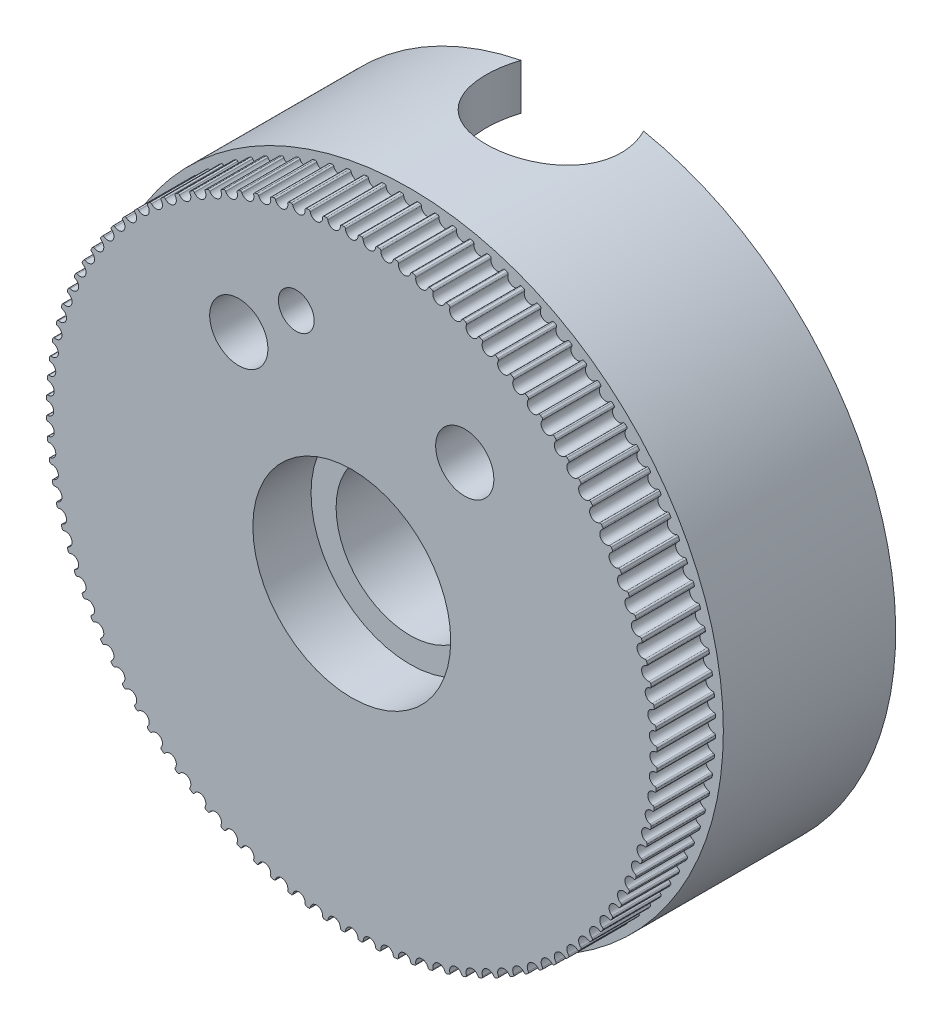
SolidWorks part; units mm, degrees
ref_plane "前视基准面" through (0, 0, 0) normal (0, 0, 1) x (1, 0, 0)
ref_plane "上视基准面" through (0, 0, 0) normal (0, 1, 0) x (1, 0, 0)
ref_plane "右视基准面" through (0, 0, 0) normal (1, 0, 0) x (0, 0, -1)
sketch "草图1" plane through (0, 0, 0) normal (0, 0, 1) x (1, 0, 0)
  circle A0 centre (0, 0) radius 35
  circle A1 centre (0, 0) radius 8.25
  dimension "D1" = 70
  dimension "D2" = 16.5
extrude "凸台-拉伸1" add sketch "草图1" along normal blind 19.25
ref_plane "基准面1" through (0, 14, 0) normal (0, 1, 0) x (1, 0, 0)
sketch "草图2" plane through (0, 14, 0) normal (0, 1, 0) x (1, 0, 0)
  line L0 (35, 0) -> (-35, 0) construction
  circle A0 centre (0, -3.2) radius 7.55
  dimension "D1" = 15.1
  dimension "D2" = 3.2
extrude "切除-拉伸1" cut sketch "草图2" along normal through all
sketch "草图3" plane through (0, 0, 0) normal (0, 0, -1) x (-1, 0, 0)
  circle A0 centre (0, 0) radius 14.5
  circle A1 centre (0, 0) radius 30
  dimension "D1" = 60
  dimension "D2" = 29
extrude "切除-拉伸2" cut sketch "草图3" against normal blind 8.75
sketch "草图4" plane through (0, 0, 19.25) normal (0, 0, 1) x (1, 0, 0)
  circle A0 centre (0, 0) radius 8.25 construction
  circle A1 centre (0, 0) radius 8.25
  arc B0 (1.1216, 34.1041) -> (0.8633, 34.1116) centre (0, 0) ccw
  arc B1 (1.2763, 33.9415) -> (1.1216, 34.1041) centre (1.1163, 33.9441) ccw
  arc B2 (0.8633, 34.1116) -> (0.6994, 33.9583) centre (0.8593, 33.9516) ccw
  arc B3 (1.2763, 33.9415) -> (2.6727, 33.8602) centre (1.9762, 33.93) ccw
  arc B4 (-0.8633, 34.1116) -> (-1.1216, 34.1041) centre (0, 0) ccw
  arc B5 (-0.6994, 33.9583) -> (-0.8633, 34.1116) centre (-0.8593, 33.9516) ccw
  arc B6 (-1.1216, 34.1041) -> (-1.2763, 33.9415) centre (-1.1163, 33.9441) ccw
  arc B7 (-0.6994, 33.9583) -> (0.6994, 33.9583) centre (0, 33.9875) ccw
  arc B8 (-2.8453, 34.0037) -> (-3.1027, 33.9812) centre (0, 0) ccw
  arc B9 (-2.6727, 33.8602) -> (-2.8453, 34.0037) centre (-2.8319, 33.8442) ccw
  arc B10 (-3.1027, 33.9812) -> (-3.2477, 33.8099) centre (-3.0881, 33.8218) ccw
  arc B11 (-2.6727, 33.8602) -> (-1.2763, 33.9415) centre (-1.9762, 33.93) ccw
  arc B12 (-4.8176, 33.7807) -> (-5.0732, 33.7433) centre (0, 0) ccw
  arc B13 (-4.637, 33.6475) -> (-4.8176, 33.7807) centre (-4.795, 33.6223) ccw
  arc B14 (-5.0732, 33.7433) -> (-5.208, 33.5638) centre (-5.0494, 33.585) ccw
  arc B15 (-4.637, 33.6475) -> (-3.2477, 33.8099) centre (-3.9457, 33.7577) ccw
  arc B16 (-6.7736, 33.4434) -> (-7.0266, 33.3912) centre (0, 0) ccw
  arc B17 (-6.5856, 33.321) -> (-6.7736, 33.4434) centre (-6.7418, 33.2866) ccw
  arc B18 (-7.0266, 33.3912) -> (-7.1508, 33.2042) centre (-6.9937, 33.2346) ccw
  arc B19 (-6.5856, 33.321) -> (-5.208, 33.5638) centre (-5.9019, 33.4712) ccw
  arc B20 (-8.7067, 32.993) -> (-8.9563, 32.9261) centre (0, 0) ccw
  arc B21 (-8.5119, 32.8817) -> (-8.7067, 32.993) centre (-8.6659, 32.8383) ccw
  arc B22 (-8.9563, 32.9261) -> (-9.0693, 32.7323) centre (-8.9143, 32.7717) ccw
  arc B23 (-8.5119, 32.8817) -> (-7.1508, 33.2042) centre (-7.8381, 33.0714) ccw
  arc B24 (-10.6103, 32.4309) -> (-10.8556, 32.3497) centre (0, 0) ccw
  arc B25 (-10.4094, 32.3311) -> (-10.6103, 32.4309) centre (-10.5606, 32.2789) ccw
  arc B26 (-10.8556, 32.3497) -> (-10.9572, 32.1496) centre (-10.8047, 32.198) ccw
  arc B27 (-10.4094, 32.3311) -> (-9.0693, 32.7323) centre (-9.7477, 32.5597) ccw
  arc B28 (-12.4781, 31.7591) -> (-12.7182, 31.6637) centre (0, 0) ccw
  arc B29 (-12.2716, 31.6712) -> (-12.4781, 31.7591) centre (-12.4196, 31.6102) ccw
  arc B30 (-12.7182, 31.6637) -> (-12.808, 31.4581) centre (-12.6586, 31.5153) ccw
  arc B31 (-12.2716, 31.6712) -> (-10.9572, 32.1496) centre (-11.6244, 31.9378) ccw
  arc B32 (-14.3036, 30.9799) -> (-14.5378, 30.8707) centre (0, 0) ccw
  arc B33 (-14.0924, 30.904) -> (-14.3036, 30.9799) centre (-14.2365, 30.8346) ccw
  arc B34 (-14.5378, 30.8707) -> (-14.6155, 30.6601) centre (-14.4696, 30.7259) ccw
  arc B35 (-14.0924, 30.904) -> (-12.808, 31.4581) centre (-13.4618, 31.2079) ccw
  arc B36 (-16.0807, 30.0958) -> (-16.3081, 29.9731) centre (0, 0) ccw
  arc B37 (-15.8655, 30.0324) -> (-16.0807, 30.0958) centre (-16.0053, 29.9547) ccw
  arc B38 (-16.3081, 29.9731) -> (-16.3735, 29.7584) centre (-16.2317, 29.8326) ccw
  arc B39 (-15.8655, 30.0324) -> (-14.6155, 30.6601) centre (-15.2536, 30.3723) ccw
  arc B40 (-17.8034, 29.1098) -> (-18.0233, 28.9742) centre (0, 0) ccw
  arc B41 (-17.5848, 29.0591) -> (-17.8034, 29.1098) centre (-17.7199, 28.9733) ccw
  arc B42 (-18.0233, 28.9742) -> (-18.0761, 28.7561) centre (-17.9388, 28.8383) ccw
  arc B43 (-17.5848, 29.0591) -> (-16.3735, 29.7584) centre (-16.9937, 29.434) ccw
  arc B44 (-19.4659, 28.0254) -> (-19.6775, 27.8772) centre (0, 0) ccw
  arc B45 (-19.2447, 27.9874) -> (-19.4659, 28.0254) centre (-19.3746, 27.894) ccw
  arc B46 (-19.6775, 27.8772) -> (-19.7175, 27.6564) centre (-19.5853, 27.7465) ccw
  arc B47 (-19.2447, 27.9874) -> (-18.0761, 28.7561) centre (-18.6764, 28.3961) ccw
  arc B48 (-21.0625, 26.8462) -> (-21.2652, 26.6859) centre (0, 0) ccw
  arc B49 (-20.8395, 26.8211) -> (-21.0625, 26.8462) centre (-20.9637, 26.7203) ccw
  arc B50 (-21.2652, 26.6859) -> (-21.2922, 26.4631) centre (-21.1655, 26.5608) ccw
  arc B51 (-20.8395, 26.8211) -> (-19.7175, 27.6564) centre (-20.2959, 27.2622) ccw
  arc B52 (-22.5878, 25.5761) -> (-22.7808, 25.4043) centre (0, 0) ccw
  arc B53 (-22.3637, 25.564) -> (-22.5878, 25.5761) centre (-22.4819, 25.4561) ccw
  arc B54 (-22.7808, 25.4043) -> (-22.7949, 25.1803) centre (-22.674, 25.2852) ccw
  arc B55 (-22.3637, 25.564) -> (-21.2922, 26.4631) centre (-21.8467, 26.0359) ccw
  arc B56 (-24.0367, 24.2194) -> (-24.2194, 24.0367) centre (0, 0) ccw
  arc B57 (-23.8123, 24.2204) -> (-24.0367, 24.2194) centre (-23.924, 24.1059) ccw
  arc B58 (-24.2194, 24.0367) -> (-24.2204, 23.8123) centre (-24.1059, 23.924) ccw
  arc B59 (-23.8123, 24.2204) -> (-22.7949, 25.1803) centre (-23.3236, 24.7216) ccw
  arc B60 (-25.4043, 22.7808) -> (-25.5761, 22.5878) centre (0, 0) ccw
  arc B61 (-25.1803, 22.7949) -> (-25.4043, 22.7808) centre (-25.2852, 22.674) ccw
  arc B62 (-25.5761, 22.5878) -> (-25.564, 22.3637) centre (-25.4561, 22.4819) ccw
  arc B63 (-25.1803, 22.7949) -> (-24.2204, 23.8123) centre (-24.7216, 23.3236) ccw
  arc B64 (-26.6859, 21.2652) -> (-26.8462, 21.0625) centre (0, 0) ccw
  arc B65 (-26.4631, 21.2922) -> (-26.6859, 21.2652) centre (-26.5608, 21.1655) ccw
  arc B66 (-26.8462, 21.0625) -> (-26.8211, 20.8395) centre (-26.7203, 20.9637) ccw
  arc B67 (-26.4631, 21.2922) -> (-25.564, 22.3637) centre (-26.0359, 21.8467) ccw
  arc B68 (-27.8772, 19.6775) -> (-28.0254, 19.4659) centre (0, 0) ccw
  arc B69 (-27.6564, 19.7175) -> (-27.8772, 19.6775) centre (-27.7465, 19.5853) ccw
  arc B70 (-28.0254, 19.4659) -> (-27.9874, 19.2447) centre (-27.894, 19.3746) ccw
  arc B71 (-27.6564, 19.7175) -> (-26.8211, 20.8395) centre (-27.2622, 20.2959) ccw
  arc B72 (-28.9742, 18.0233) -> (-29.1098, 17.8034) centre (0, 0) ccw
  arc B73 (-28.7561, 18.0761) -> (-28.9742, 18.0233) centre (-28.8383, 17.9388) ccw
  arc B74 (-29.1098, 17.8034) -> (-29.0591, 17.5848) centre (-28.9733, 17.7199) ccw
  arc B75 (-28.7561, 18.0761) -> (-27.9874, 19.2447) centre (-28.3961, 18.6764) ccw
  arc B76 (-29.9731, 16.3081) -> (-30.0958, 16.0807) centre (0, 0) ccw
  arc B77 (-29.7584, 16.3735) -> (-29.9731, 16.3081) centre (-29.8326, 16.2317) ccw
  arc B78 (-30.0958, 16.0807) -> (-30.0324, 15.8655) centre (-29.9547, 16.0053) ccw
  arc B79 (-29.7584, 16.3735) -> (-29.0591, 17.5848) centre (-29.434, 16.9937) ccw
  arc B80 (-30.8707, 14.5378) -> (-30.9799, 14.3036) centre (0, 0) ccw
  arc B81 (-30.6601, 14.6155) -> (-30.8707, 14.5378) centre (-30.7259, 14.4696) ccw
  arc B82 (-30.9799, 14.3036) -> (-30.904, 14.0924) centre (-30.8346, 14.2365) ccw
  arc B83 (-30.6601, 14.6155) -> (-30.0324, 15.8655) centre (-30.3723, 15.2536) ccw
  arc B84 (-31.6637, 12.7182) -> (-31.7591, 12.4781) centre (0, 0) ccw
  arc B85 (-31.4581, 12.808) -> (-31.6637, 12.7182) centre (-31.5153, 12.6586) ccw
  arc B86 (-31.7591, 12.4781) -> (-31.6712, 12.2716) centre (-31.6102, 12.4196) ccw
  arc B87 (-31.4581, 12.808) -> (-30.904, 14.0924) centre (-31.2079, 13.4618) ccw
  arc B88 (-32.3497, 10.8556) -> (-32.4309, 10.6103) centre (0, 0) ccw
  arc B89 (-32.1496, 10.9572) -> (-32.3497, 10.8556) centre (-32.198, 10.8047) ccw
  arc B90 (-32.4309, 10.6103) -> (-32.3311, 10.4094) centre (-32.2789, 10.5606) ccw
  arc B91 (-32.1496, 10.9572) -> (-31.6712, 12.2716) centre (-31.9378, 11.6244) ccw
  arc B92 (-32.9261, 8.9563) -> (-32.993, 8.7067) centre (0, 0) ccw
  arc B93 (-32.7323, 9.0693) -> (-32.9261, 8.9563) centre (-32.7717, 8.9143) ccw
  arc B94 (-32.993, 8.7067) -> (-32.8817, 8.5119) centre (-32.8383, 8.6659) ccw
  arc B95 (-32.7323, 9.0693) -> (-32.3311, 10.4094) centre (-32.5597, 9.7477) ccw
  arc B96 (-33.3912, 7.0266) -> (-33.4434, 6.7736) centre (0, 0) ccw
  arc B97 (-33.2042, 7.1508) -> (-33.3912, 7.0266) centre (-33.2346, 6.9937) ccw
  arc B98 (-33.4434, 6.7736) -> (-33.321, 6.5856) centre (-33.2866, 6.7418) ccw
  arc B99 (-33.2042, 7.1508) -> (-32.8817, 8.5119) centre (-33.0714, 7.8381) ccw
  arc B100 (-33.7433, 5.0732) -> (-33.7807, 4.8176) centre (0, 0) ccw
  arc B101 (-33.5638, 5.208) -> (-33.7433, 5.0732) centre (-33.585, 5.0494) ccw
  arc B102 (-33.7807, 4.8176) -> (-33.6475, 4.637) centre (-33.6223, 4.795) ccw
  arc B103 (-33.5638, 5.208) -> (-33.321, 6.5856) centre (-33.4712, 5.9019) ccw
  arc B104 (-33.9812, 3.1027) -> (-34.0037, 2.8453) centre (0, 0) ccw
  arc B105 (-33.8099, 3.2477) -> (-33.9812, 3.1027) centre (-33.8218, 3.0881) ccw
  arc B106 (-34.0037, 2.8453) -> (-33.8602, 2.6727) centre (-33.8442, 2.8319) ccw
  arc B107 (-33.8099, 3.2477) -> (-33.6475, 4.637) centre (-33.7577, 3.9457) ccw
  arc B108 (-34.1041, 1.1216) -> (-34.1116, 0.8633) centre (0, 0) ccw
  arc B109 (-33.9415, 1.2763) -> (-34.1041, 1.1216) centre (-33.9441, 1.1163) ccw
  arc B110 (-34.1116, 0.8633) -> (-33.9583, 0.6994) centre (-33.9516, 0.8593) ccw
  arc B111 (-33.9415, 1.2763) -> (-33.8602, 2.6727) centre (-33.93, 1.9762) ccw
  arc B112 (-34.1116, -0.8633) -> (-34.1041, -1.1216) centre (0, 0) ccw
  arc B113 (-33.9583, -0.6994) -> (-34.1116, -0.8633) centre (-33.9516, -0.8593) ccw
  arc B114 (-34.1041, -1.1216) -> (-33.9415, -1.2763) centre (-33.9441, -1.1163) ccw
  arc B115 (-33.9583, -0.6994) -> (-33.9583, 0.6994) centre (-33.9875, 0) ccw
  arc B116 (-34.0037, -2.8453) -> (-33.9812, -3.1027) centre (0, 0) ccw
  arc B117 (-33.8602, -2.6727) -> (-34.0037, -2.8453) centre (-33.8442, -2.8319) ccw
  arc B118 (-33.9812, -3.1027) -> (-33.8099, -3.2477) centre (-33.8218, -3.0881) ccw
  arc B119 (-33.8602, -2.6727) -> (-33.9415, -1.2763) centre (-33.93, -1.9762) ccw
  arc B120 (-33.7807, -4.8176) -> (-33.7433, -5.0732) centre (0, 0) ccw
  arc B121 (-33.6475, -4.637) -> (-33.7807, -4.8176) centre (-33.6223, -4.795) ccw
  arc B122 (-33.7433, -5.0732) -> (-33.5638, -5.208) centre (-33.585, -5.0494) ccw
  arc B123 (-33.6475, -4.637) -> (-33.8099, -3.2477) centre (-33.7577, -3.9457) ccw
  arc B124 (-33.4434, -6.7736) -> (-33.3912, -7.0266) centre (0, 0) ccw
  arc B125 (-33.321, -6.5856) -> (-33.4434, -6.7736) centre (-33.2866, -6.7418) ccw
  arc B126 (-33.3912, -7.0266) -> (-33.2042, -7.1508) centre (-33.2346, -6.9937) ccw
  arc B127 (-33.321, -6.5856) -> (-33.5638, -5.208) centre (-33.4712, -5.9019) ccw
  arc B128 (-32.993, -8.7067) -> (-32.9261, -8.9563) centre (0, 0) ccw
  arc B129 (-32.8817, -8.5119) -> (-32.993, -8.7067) centre (-32.8383, -8.6659) ccw
  arc B130 (-32.9261, -8.9563) -> (-32.7323, -9.0693) centre (-32.7717, -8.9143) ccw
  arc B131 (-32.8817, -8.5119) -> (-33.2042, -7.1508) centre (-33.0714, -7.8381) ccw
  arc B132 (-32.4309, -10.6103) -> (-32.3497, -10.8556) centre (0, 0) ccw
  arc B133 (-32.3311, -10.4094) -> (-32.4309, -10.6103) centre (-32.2789, -10.5606) ccw
  arc B134 (-32.3497, -10.8556) -> (-32.1496, -10.9572) centre (-32.198, -10.8047) ccw
  arc B135 (-32.3311, -10.4094) -> (-32.7323, -9.0693) centre (-32.5597, -9.7477) ccw
  arc B136 (-31.7591, -12.4781) -> (-31.6637, -12.7182) centre (0, 0) ccw
  arc B137 (-31.6712, -12.2716) -> (-31.7591, -12.4781) centre (-31.6102, -12.4196) ccw
  arc B138 (-31.6637, -12.7182) -> (-31.4581, -12.808) centre (-31.5153, -12.6586) ccw
  arc B139 (-31.6712, -12.2716) -> (-32.1496, -10.9572) centre (-31.9378, -11.6244) ccw
  arc B140 (-30.9799, -14.3036) -> (-30.8707, -14.5378) centre (0, 0) ccw
  arc B141 (-30.904, -14.0924) -> (-30.9799, -14.3036) centre (-30.8346, -14.2365) ccw
  arc B142 (-30.8707, -14.5378) -> (-30.6601, -14.6155) centre (-30.7259, -14.4696) ccw
  arc B143 (-30.904, -14.0924) -> (-31.4581, -12.808) centre (-31.2079, -13.4618) ccw
  arc B144 (-30.0958, -16.0807) -> (-29.9731, -16.3081) centre (0, 0) ccw
  arc B145 (-30.0324, -15.8655) -> (-30.0958, -16.0807) centre (-29.9547, -16.0053) ccw
  arc B146 (-29.9731, -16.3081) -> (-29.7584, -16.3735) centre (-29.8326, -16.2317) ccw
  arc B147 (-30.0324, -15.8655) -> (-30.6601, -14.6155) centre (-30.3723, -15.2536) ccw
  arc B148 (-29.1098, -17.8034) -> (-28.9742, -18.0233) centre (0, 0) ccw
  arc B149 (-29.0591, -17.5848) -> (-29.1098, -17.8034) centre (-28.9733, -17.7199) ccw
  arc B150 (-28.9742, -18.0233) -> (-28.7561, -18.0761) centre (-28.8383, -17.9388) ccw
  arc B151 (-29.0591, -17.5848) -> (-29.7584, -16.3735) centre (-29.434, -16.9938) ccw
  arc B152 (-28.0254, -19.4659) -> (-27.8772, -19.6775) centre (0, 0) ccw
  arc B153 (-27.9874, -19.2447) -> (-28.0254, -19.4659) centre (-27.894, -19.3746) ccw
  arc B154 (-27.8772, -19.6775) -> (-27.6564, -19.7175) centre (-27.7465, -19.5853) ccw
  arc B155 (-27.9874, -19.2447) -> (-28.7561, -18.0761) centre (-28.3961, -18.6764) ccw
  arc B156 (-26.8462, -21.0625) -> (-26.6859, -21.2652) centre (0, 0) ccw
  arc B157 (-26.8211, -20.8395) -> (-26.8462, -21.0625) centre (-26.7203, -20.9637) ccw
  arc B158 (-26.6859, -21.2652) -> (-26.4631, -21.2922) centre (-26.5608, -21.1655) ccw
  arc B159 (-26.8211, -20.8395) -> (-27.6564, -19.7175) centre (-27.2622, -20.2959) ccw
  arc B160 (-25.5761, -22.5878) -> (-25.4043, -22.7808) centre (0, 0) ccw
  arc B161 (-25.564, -22.3637) -> (-25.5761, -22.5878) centre (-25.4561, -22.4819) ccw
  arc B162 (-25.4043, -22.7808) -> (-25.1803, -22.7949) centre (-25.2852, -22.674) ccw
  arc B163 (-25.564, -22.3637) -> (-26.4631, -21.2922) centre (-26.0359, -21.8467) ccw
  arc B164 (-24.2194, -24.0367) -> (-24.0367, -24.2194) centre (0, 0) ccw
  arc B165 (-24.2204, -23.8123) -> (-24.2194, -24.0367) centre (-24.1059, -23.924) ccw
  arc B166 (-24.0367, -24.2194) -> (-23.8123, -24.2204) centre (-23.924, -24.1059) ccw
  arc B167 (-24.2204, -23.8123) -> (-25.1803, -22.7949) centre (-24.7216, -23.3236) ccw
  arc B168 (-22.7808, -25.4043) -> (-22.5878, -25.5761) centre (0, 0) ccw
  arc B169 (-22.7949, -25.1803) -> (-22.7808, -25.4043) centre (-22.674, -25.2852) ccw
  arc B170 (-22.5878, -25.5761) -> (-22.3637, -25.564) centre (-22.4819, -25.4561) ccw
  arc B171 (-22.7949, -25.1803) -> (-23.8123, -24.2204) centre (-23.3236, -24.7216) ccw
  arc B172 (-21.2652, -26.6859) -> (-21.0625, -26.8462) centre (0, 0) ccw
  arc B173 (-21.2922, -26.4631) -> (-21.2652, -26.6859) centre (-21.1655, -26.5608) ccw
  arc B174 (-21.0625, -26.8462) -> (-20.8395, -26.8211) centre (-20.9637, -26.7203) ccw
  arc B175 (-21.2922, -26.4631) -> (-22.3637, -25.564) centre (-21.8467, -26.0359) ccw
  arc B176 (-19.6775, -27.8772) -> (-19.4659, -28.0254) centre (0, 0) ccw
  arc B177 (-19.7175, -27.6564) -> (-19.6775, -27.8772) centre (-19.5853, -27.7465) ccw
  arc B178 (-19.4659, -28.0254) -> (-19.2447, -27.9874) centre (-19.3746, -27.894) ccw
  arc B179 (-19.7175, -27.6564) -> (-20.8395, -26.8211) centre (-20.2959, -27.2622) ccw
  arc B180 (-18.0233, -28.9742) -> (-17.8034, -29.1098) centre (0, 0) ccw
  arc B181 (-18.0761, -28.7561) -> (-18.0233, -28.9742) centre (-17.9388, -28.8383) ccw
  arc B182 (-17.8034, -29.1098) -> (-17.5848, -29.0591) centre (-17.7199, -28.9733) ccw
  arc B183 (-18.0761, -28.7561) -> (-19.2447, -27.9874) centre (-18.6764, -28.3961) ccw
  arc B184 (-16.3081, -29.9731) -> (-16.0807, -30.0958) centre (0, 0) ccw
  arc B185 (-16.3735, -29.7584) -> (-16.3081, -29.9731) centre (-16.2317, -29.8326) ccw
  arc B186 (-16.0807, -30.0958) -> (-15.8655, -30.0324) centre (-16.0053, -29.9547) ccw
  arc B187 (-16.3735, -29.7584) -> (-17.5848, -29.0591) centre (-16.9937, -29.434) ccw
  arc B188 (-14.5378, -30.8707) -> (-14.3036, -30.9799) centre (0, 0) ccw
  arc B189 (-14.6155, -30.6601) -> (-14.5378, -30.8707) centre (-14.4696, -30.7259) ccw
  arc B190 (-14.3036, -30.9799) -> (-14.0924, -30.904) centre (-14.2365, -30.8346) ccw
  arc B191 (-14.6155, -30.6601) -> (-15.8655, -30.0324) centre (-15.2536, -30.3723) ccw
  arc B192 (-12.7182, -31.6637) -> (-12.4781, -31.7591) centre (0, 0) ccw
  arc B193 (-12.808, -31.4581) -> (-12.7182, -31.6637) centre (-12.6586, -31.5153) ccw
  arc B194 (-12.4781, -31.7591) -> (-12.2716, -31.6712) centre (-12.4196, -31.6102) ccw
  arc B195 (-12.808, -31.4581) -> (-14.0924, -30.904) centre (-13.4618, -31.2079) ccw
  arc B196 (-10.8556, -32.3497) -> (-10.6103, -32.4309) centre (0, 0) ccw
  arc B197 (-10.9572, -32.1496) -> (-10.8556, -32.3497) centre (-10.8047, -32.198) ccw
  arc B198 (-10.6103, -32.4309) -> (-10.4094, -32.3311) centre (-10.5606, -32.2789) ccw
  arc B199 (-10.9572, -32.1496) -> (-12.2716, -31.6712) centre (-11.6244, -31.9378) ccw
  arc B200 (-8.9563, -32.9261) -> (-8.7067, -32.993) centre (0, 0) ccw
  arc B201 (-9.0693, -32.7323) -> (-8.9563, -32.9261) centre (-8.9143, -32.7717) ccw
  arc B202 (-8.7067, -32.993) -> (-8.5119, -32.8817) centre (-8.6659, -32.8383) ccw
  arc B203 (-9.0693, -32.7323) -> (-10.4094, -32.3311) centre (-9.7477, -32.5597) ccw
  arc B204 (-7.0266, -33.3912) -> (-6.7736, -33.4434) centre (0, 0) ccw
  arc B205 (-7.1508, -33.2042) -> (-7.0266, -33.3912) centre (-6.9937, -33.2346) ccw
  arc B206 (-6.7736, -33.4434) -> (-6.5856, -33.321) centre (-6.7418, -33.2866) ccw
  arc B207 (-7.1508, -33.2042) -> (-8.5119, -32.8817) centre (-7.8381, -33.0714) ccw
  arc B208 (-5.0732, -33.7433) -> (-4.8176, -33.7807) centre (0, 0) ccw
  arc B209 (-5.208, -33.5638) -> (-5.0732, -33.7433) centre (-5.0494, -33.585) ccw
  arc B210 (-4.8176, -33.7807) -> (-4.637, -33.6475) centre (-4.795, -33.6223) ccw
  arc B211 (-5.208, -33.5638) -> (-6.5856, -33.321) centre (-5.9019, -33.4712) ccw
  arc B212 (-3.1027, -33.9812) -> (-2.8453, -34.0037) centre (0, 0) ccw
  arc B213 (-3.2477, -33.8099) -> (-3.1027, -33.9812) centre (-3.0881, -33.8218) ccw
  arc B214 (-2.8453, -34.0037) -> (-2.6727, -33.8602) centre (-2.8319, -33.8442) ccw
  arc B215 (-3.2477, -33.8099) -> (-4.637, -33.6475) centre (-3.9457, -33.7577) ccw
  arc B216 (-1.1216, -34.1041) -> (-0.8633, -34.1116) centre (0, 0) ccw
  arc B217 (-1.2763, -33.9415) -> (-1.1216, -34.1041) centre (-1.1163, -33.9441) ccw
  arc B218 (-0.8633, -34.1116) -> (-0.6994, -33.9583) centre (-0.8593, -33.9516) ccw
  arc B219 (-1.2763, -33.9415) -> (-2.6727, -33.8602) centre (-1.9762, -33.93) ccw
  arc B220 (0.8633, -34.1116) -> (1.1216, -34.1041) centre (0, 0) ccw
  arc B221 (0.6994, -33.9583) -> (0.8633, -34.1116) centre (0.8593, -33.9516) ccw
  arc B222 (1.1216, -34.1041) -> (1.2763, -33.9415) centre (1.1163, -33.9441) ccw
  arc B223 (0.6994, -33.9583) -> (-0.6994, -33.9583) centre (0, -33.9875) ccw
  arc B224 (2.8453, -34.0037) -> (3.1027, -33.9812) centre (0, 0) ccw
  arc B225 (2.6727, -33.8602) -> (2.8453, -34.0037) centre (2.8319, -33.8442) ccw
  arc B226 (3.1027, -33.9812) -> (3.2477, -33.8099) centre (3.0881, -33.8218) ccw
  arc B227 (2.6727, -33.8602) -> (1.2763, -33.9415) centre (1.9762, -33.93) ccw
  arc B228 (4.8176, -33.7807) -> (5.0732, -33.7433) centre (0, 0) ccw
  arc B229 (4.637, -33.6475) -> (4.8176, -33.7807) centre (4.795, -33.6223) ccw
  arc B230 (5.0732, -33.7433) -> (5.208, -33.5638) centre (5.0494, -33.585) ccw
  arc B231 (4.637, -33.6475) -> (3.2477, -33.8099) centre (3.9457, -33.7577) ccw
  arc B232 (6.7736, -33.4434) -> (7.0266, -33.3912) centre (0, 0) ccw
  arc B233 (6.5856, -33.321) -> (6.7736, -33.4434) centre (6.7418, -33.2866) ccw
  arc B234 (7.0266, -33.3912) -> (7.1508, -33.2042) centre (6.9937, -33.2346) ccw
  arc B235 (6.5856, -33.321) -> (5.208, -33.5638) centre (5.9019, -33.4712) ccw
  arc B236 (8.7067, -32.993) -> (8.9563, -32.9261) centre (0, 0) ccw
  arc B237 (8.5119, -32.8817) -> (8.7067, -32.993) centre (8.6659, -32.8383) ccw
  arc B238 (8.9563, -32.9261) -> (9.0693, -32.7323) centre (8.9143, -32.7717) ccw
  arc B239 (8.5119, -32.8817) -> (7.1508, -33.2042) centre (7.8381, -33.0714) ccw
  arc B240 (10.6103, -32.4309) -> (10.8556, -32.3497) centre (0, 0) ccw
  arc B241 (10.4094, -32.3311) -> (10.6103, -32.4309) centre (10.5606, -32.2789) ccw
  arc B242 (10.8556, -32.3497) -> (10.9572, -32.1496) centre (10.8047, -32.198) ccw
  arc B243 (10.4094, -32.3311) -> (9.0693, -32.7323) centre (9.7477, -32.5597) ccw
  arc B244 (12.4781, -31.7591) -> (12.7182, -31.6637) centre (0, 0) ccw
  arc B245 (12.2716, -31.6712) -> (12.4781, -31.7591) centre (12.4196, -31.6102) ccw
  arc B246 (12.7182, -31.6637) -> (12.808, -31.4581) centre (12.6586, -31.5153) ccw
  arc B247 (12.2716, -31.6712) -> (10.9572, -32.1496) centre (11.6244, -31.9378) ccw
  arc B248 (14.3036, -30.9799) -> (14.5378, -30.8707) centre (0, 0) ccw
  arc B249 (14.0924, -30.904) -> (14.3036, -30.9799) centre (14.2365, -30.8346) ccw
  arc B250 (14.5378, -30.8707) -> (14.6155, -30.6601) centre (14.4696, -30.7259) ccw
  arc B251 (14.0924, -30.904) -> (12.808, -31.4581) centre (13.4618, -31.2079) ccw
  arc B252 (16.0807, -30.0958) -> (16.3081, -29.9731) centre (0, 0) ccw
  arc B253 (15.8655, -30.0324) -> (16.0807, -30.0958) centre (16.0053, -29.9547) ccw
  arc B254 (16.3081, -29.9731) -> (16.3735, -29.7584) centre (16.2317, -29.8326) ccw
  arc B255 (15.8655, -30.0324) -> (14.6155, -30.6601) centre (15.2536, -30.3723) ccw
  arc B256 (17.8034, -29.1098) -> (18.0233, -28.9742) centre (0, 0) ccw
  arc B257 (17.5848, -29.0591) -> (17.8034, -29.1098) centre (17.7199, -28.9733) ccw
  arc B258 (18.0233, -28.9742) -> (18.0761, -28.7561) centre (17.9388, -28.8383) ccw
  arc B259 (17.5848, -29.0591) -> (16.3735, -29.7584) centre (16.9938, -29.434) ccw
  arc B260 (19.4659, -28.0254) -> (19.6775, -27.8772) centre (0, 0) ccw
  arc B261 (19.2447, -27.9874) -> (19.4659, -28.0254) centre (19.3746, -27.894) ccw
  arc B262 (19.6775, -27.8772) -> (19.7175, -27.6564) centre (19.5853, -27.7465) ccw
  arc B263 (19.2447, -27.9874) -> (18.0761, -28.7561) centre (18.6764, -28.3961) ccw
  arc B264 (21.0625, -26.8462) -> (21.2652, -26.6859) centre (0, 0) ccw
  arc B265 (20.8395, -26.8211) -> (21.0625, -26.8462) centre (20.9637, -26.7203) ccw
  arc B266 (21.2652, -26.6859) -> (21.2922, -26.4631) centre (21.1655, -26.5608) ccw
  arc B267 (20.8395, -26.8211) -> (19.7175, -27.6564) centre (20.2959, -27.2622) ccw
  arc B268 (22.5878, -25.5761) -> (22.7808, -25.4043) centre (0, 0) ccw
  arc B269 (22.3637, -25.564) -> (22.5878, -25.5761) centre (22.4819, -25.4561) ccw
  arc B270 (22.7808, -25.4043) -> (22.7949, -25.1803) centre (22.674, -25.2852) ccw
  arc B271 (22.3637, -25.564) -> (21.2922, -26.4631) centre (21.8467, -26.0359) ccw
  arc B272 (24.0367, -24.2194) -> (24.2194, -24.0367) centre (0, 0) ccw
  arc B273 (23.8123, -24.2204) -> (24.0367, -24.2194) centre (23.924, -24.1059) ccw
  arc B274 (24.2194, -24.0367) -> (24.2204, -23.8123) centre (24.1059, -23.924) ccw
  arc B275 (23.8123, -24.2204) -> (22.7949, -25.1803) centre (23.3236, -24.7216) ccw
  arc B276 (25.4043, -22.7808) -> (25.5761, -22.5878) centre (0, 0) ccw
  arc B277 (25.1803, -22.7949) -> (25.4043, -22.7808) centre (25.2852, -22.674) ccw
  arc B278 (25.5761, -22.5878) -> (25.564, -22.3637) centre (25.4561, -22.4819) ccw
  arc B279 (25.1803, -22.7949) -> (24.2204, -23.8123) centre (24.7216, -23.3236) ccw
  arc B280 (26.6859, -21.2652) -> (26.8462, -21.0625) centre (0, 0) ccw
  arc B281 (26.4631, -21.2922) -> (26.6859, -21.2652) centre (26.5608, -21.1655) ccw
  arc B282 (26.8462, -21.0625) -> (26.8211, -20.8395) centre (26.7203, -20.9637) ccw
  arc B283 (26.4631, -21.2922) -> (25.564, -22.3637) centre (26.0359, -21.8467) ccw
  arc B284 (27.8772, -19.6775) -> (28.0254, -19.4659) centre (0, 0) ccw
  arc B285 (27.6564, -19.7175) -> (27.8772, -19.6775) centre (27.7465, -19.5853) ccw
  arc B286 (28.0254, -19.4659) -> (27.9874, -19.2447) centre (27.894, -19.3746) ccw
  arc B287 (27.6564, -19.7175) -> (26.8211, -20.8395) centre (27.2622, -20.2959) ccw
  arc B288 (28.9742, -18.0233) -> (29.1098, -17.8034) centre (0, 0) ccw
  arc B289 (28.7561, -18.0761) -> (28.9742, -18.0233) centre (28.8383, -17.9388) ccw
  arc B290 (29.1098, -17.8034) -> (29.0591, -17.5848) centre (28.9733, -17.7199) ccw
  arc B291 (28.7561, -18.0761) -> (27.9874, -19.2447) centre (28.3961, -18.6764) ccw
  arc B292 (29.9731, -16.3081) -> (30.0958, -16.0807) centre (0, 0) ccw
  arc B293 (29.7584, -16.3735) -> (29.9731, -16.3081) centre (29.8326, -16.2317) ccw
  arc B294 (30.0958, -16.0807) -> (30.0324, -15.8655) centre (29.9547, -16.0053) ccw
  arc B295 (29.7584, -16.3735) -> (29.0591, -17.5848) centre (29.434, -16.9938) ccw
  arc B296 (30.8707, -14.5378) -> (30.9799, -14.3036) centre (0, 0) ccw
  arc B297 (30.6601, -14.6155) -> (30.8707, -14.5378) centre (30.7259, -14.4696) ccw
  arc B298 (30.9799, -14.3036) -> (30.904, -14.0924) centre (30.8346, -14.2365) ccw
  arc B299 (30.6601, -14.6155) -> (30.0324, -15.8655) centre (30.3723, -15.2536) ccw
  arc B300 (31.6637, -12.7182) -> (31.7591, -12.4781) centre (0, 0) ccw
  arc B301 (31.4581, -12.808) -> (31.6637, -12.7182) centre (31.5153, -12.6586) ccw
  arc B302 (31.7591, -12.4781) -> (31.6712, -12.2716) centre (31.6102, -12.4196) ccw
  arc B303 (31.4581, -12.808) -> (30.904, -14.0924) centre (31.2079, -13.4618) ccw
  arc B304 (32.3497, -10.8556) -> (32.4309, -10.6103) centre (0, 0) ccw
  arc B305 (32.1496, -10.9572) -> (32.3497, -10.8556) centre (32.198, -10.8047) ccw
  arc B306 (32.4309, -10.6103) -> (32.3311, -10.4094) centre (32.2789, -10.5606) ccw
  arc B307 (32.1496, -10.9572) -> (31.6712, -12.2716) centre (31.9378, -11.6244) ccw
  arc B308 (32.9261, -8.9563) -> (32.993, -8.7067) centre (0, 0) ccw
  arc B309 (32.7323, -9.0693) -> (32.9261, -8.9563) centre (32.7717, -8.9143) ccw
  arc B310 (32.993, -8.7067) -> (32.8817, -8.5119) centre (32.8383, -8.6659) ccw
  arc B311 (32.7323, -9.0693) -> (32.3311, -10.4094) centre (32.5597, -9.7477) ccw
  arc B312 (33.3912, -7.0266) -> (33.4434, -6.7736) centre (0, 0) ccw
  arc B313 (33.2042, -7.1508) -> (33.3912, -7.0266) centre (33.2346, -6.9937) ccw
  arc B314 (33.4434, -6.7736) -> (33.321, -6.5856) centre (33.2866, -6.7418) ccw
  arc B315 (33.2042, -7.1508) -> (32.8817, -8.5119) centre (33.0714, -7.8381) ccw
  arc B316 (33.7433, -5.0732) -> (33.7807, -4.8176) centre (0, 0) ccw
  arc B317 (33.5638, -5.208) -> (33.7433, -5.0732) centre (33.585, -5.0494) ccw
  arc B318 (33.7807, -4.8176) -> (33.6475, -4.637) centre (33.6223, -4.795) ccw
  arc B319 (33.5638, -5.208) -> (33.321, -6.5856) centre (33.4712, -5.9019) ccw
  arc B320 (33.9812, -3.1027) -> (34.0037, -2.8453) centre (0, 0) ccw
  arc B321 (33.8099, -3.2477) -> (33.9812, -3.1027) centre (33.8218, -3.0881) ccw
  arc B322 (34.0037, -2.8453) -> (33.8602, -2.6727) centre (33.8442, -2.8319) ccw
  arc B323 (33.8099, -3.2477) -> (33.6475, -4.637) centre (33.7577, -3.9457) ccw
  arc B324 (34.1041, -1.1216) -> (34.1116, -0.8633) centre (0, 0) ccw
  arc B325 (33.9415, -1.2763) -> (34.1041, -1.1216) centre (33.9441, -1.1163) ccw
  arc B326 (34.1116, -0.8633) -> (33.9583, -0.6994) centre (33.9516, -0.8593) ccw
  arc B327 (33.9415, -1.2763) -> (33.8602, -2.6727) centre (33.93, -1.9762) ccw
  arc B328 (34.1116, 0.8633) -> (34.1041, 1.1216) centre (0, 0) ccw
  arc B329 (33.9583, 0.6994) -> (34.1116, 0.8633) centre (33.9516, 0.8593) ccw
  arc B330 (34.1041, 1.1216) -> (33.9415, 1.2763) centre (33.9441, 1.1163) ccw
  arc B331 (33.9583, 0.6994) -> (33.9583, -0.6994) centre (33.9875, 0) ccw
  arc B332 (34.0037, 2.8453) -> (33.9812, 3.1027) centre (0, 0) ccw
  arc B333 (33.8602, 2.6727) -> (34.0037, 2.8453) centre (33.8442, 2.8319) ccw
  arc B334 (33.9812, 3.1027) -> (33.8099, 3.2477) centre (33.8218, 3.0881) ccw
  arc B335 (33.8602, 2.6727) -> (33.9415, 1.2763) centre (33.93, 1.9762) ccw
  arc B336 (33.7807, 4.8176) -> (33.7433, 5.0732) centre (0, 0) ccw
  arc B337 (33.6475, 4.637) -> (33.7807, 4.8176) centre (33.6223, 4.795) ccw
  arc B338 (33.7433, 5.0732) -> (33.5638, 5.208) centre (33.585, 5.0494) ccw
  arc B339 (33.6475, 4.637) -> (33.8099, 3.2477) centre (33.7577, 3.9457) ccw
  arc B340 (33.4434, 6.7736) -> (33.3912, 7.0266) centre (0, 0) ccw
  arc B341 (33.321, 6.5856) -> (33.4434, 6.7736) centre (33.2866, 6.7418) ccw
  arc B342 (33.3912, 7.0266) -> (33.2042, 7.1508) centre (33.2346, 6.9937) ccw
  arc B343 (33.321, 6.5856) -> (33.5638, 5.208) centre (33.4712, 5.9019) ccw
  arc B344 (32.993, 8.7067) -> (32.9261, 8.9563) centre (0, 0) ccw
  arc B345 (32.8817, 8.5119) -> (32.993, 8.7067) centre (32.8383, 8.6659) ccw
  arc B346 (32.9261, 8.9563) -> (32.7323, 9.0693) centre (32.7717, 8.9143) ccw
  arc B347 (32.8817, 8.5119) -> (33.2042, 7.1508) centre (33.0714, 7.8381) ccw
  arc B348 (32.4309, 10.6103) -> (32.3497, 10.8556) centre (0, 0) ccw
  arc B349 (32.3311, 10.4094) -> (32.4309, 10.6103) centre (32.2789, 10.5606) ccw
  arc B350 (32.3497, 10.8556) -> (32.1496, 10.9572) centre (32.198, 10.8047) ccw
  arc B351 (32.3311, 10.4094) -> (32.7323, 9.0693) centre (32.5597, 9.7477) ccw
  arc B352 (31.7591, 12.4781) -> (31.6637, 12.7182) centre (0, 0) ccw
  arc B353 (31.6712, 12.2716) -> (31.7591, 12.4781) centre (31.6102, 12.4196) ccw
  arc B354 (31.6637, 12.7182) -> (31.4581, 12.808) centre (31.5153, 12.6586) ccw
  arc B355 (31.6712, 12.2716) -> (32.1496, 10.9572) centre (31.9378, 11.6244) ccw
  arc B356 (30.9799, 14.3036) -> (30.8707, 14.5378) centre (0, 0) ccw
  arc B357 (30.904, 14.0924) -> (30.9799, 14.3036) centre (30.8346, 14.2365) ccw
  arc B358 (30.8707, 14.5378) -> (30.6601, 14.6155) centre (30.7259, 14.4696) ccw
  arc B359 (30.904, 14.0924) -> (31.4581, 12.808) centre (31.2079, 13.4618) ccw
  arc B360 (30.0958, 16.0807) -> (29.9731, 16.3081) centre (0, 0) ccw
  arc B361 (30.0324, 15.8655) -> (30.0958, 16.0807) centre (29.9547, 16.0053) ccw
  arc B362 (29.9731, 16.3081) -> (29.7584, 16.3735) centre (29.8326, 16.2317) ccw
  arc B363 (30.0324, 15.8655) -> (30.6601, 14.6155) centre (30.3723, 15.2536) ccw
  arc B364 (29.1098, 17.8034) -> (28.9742, 18.0233) centre (0, 0) ccw
  arc B365 (29.0591, 17.5848) -> (29.1098, 17.8034) centre (28.9733, 17.7199) ccw
  arc B366 (28.9742, 18.0233) -> (28.7561, 18.0761) centre (28.8383, 17.9388) ccw
  arc B367 (29.0591, 17.5848) -> (29.7584, 16.3735) centre (29.434, 16.9938) ccw
  arc B368 (28.0254, 19.4659) -> (27.8772, 19.6775) centre (0, 0) ccw
  arc B369 (27.9874, 19.2447) -> (28.0254, 19.4659) centre (27.894, 19.3746) ccw
  arc B370 (27.8772, 19.6775) -> (27.6564, 19.7175) centre (27.7465, 19.5853) ccw
  arc B371 (27.9874, 19.2447) -> (28.7561, 18.0761) centre (28.3961, 18.6764) ccw
  arc B372 (26.8462, 21.0625) -> (26.6859, 21.2652) centre (0, 0) ccw
  arc B373 (26.8211, 20.8395) -> (26.8462, 21.0625) centre (26.7203, 20.9637) ccw
  arc B374 (26.6859, 21.2652) -> (26.4631, 21.2922) centre (26.5608, 21.1655) ccw
  arc B375 (26.8211, 20.8395) -> (27.6564, 19.7175) centre (27.2622, 20.2959) ccw
  arc B376 (25.5761, 22.5878) -> (25.4043, 22.7808) centre (0, 0) ccw
  arc B377 (25.564, 22.3637) -> (25.5761, 22.5878) centre (25.4561, 22.4819) ccw
  arc B378 (25.4043, 22.7808) -> (25.1803, 22.7949) centre (25.2852, 22.674) ccw
  arc B379 (25.564, 22.3637) -> (26.4631, 21.2922) centre (26.0359, 21.8467) ccw
  arc B380 (24.2194, 24.0367) -> (24.0367, 24.2194) centre (0, 0) ccw
  arc B381 (24.2204, 23.8123) -> (24.2194, 24.0367) centre (24.1059, 23.924) ccw
  arc B382 (24.0367, 24.2194) -> (23.8123, 24.2204) centre (23.924, 24.1059) ccw
  arc B383 (24.2204, 23.8123) -> (25.1803, 22.7949) centre (24.7216, 23.3236) ccw
  arc B384 (22.7808, 25.4043) -> (22.5878, 25.5761) centre (0, 0) ccw
  arc B385 (22.7949, 25.1803) -> (22.7808, 25.4043) centre (22.674, 25.2852) ccw
  arc B386 (22.5878, 25.5761) -> (22.3637, 25.564) centre (22.4819, 25.4561) ccw
  arc B387 (22.7949, 25.1803) -> (23.8123, 24.2204) centre (23.3236, 24.7216) ccw
  arc B388 (21.2652, 26.6859) -> (21.0625, 26.8462) centre (0, 0) ccw
  arc B389 (21.2922, 26.4631) -> (21.2652, 26.6859) centre (21.1655, 26.5608) ccw
  arc B390 (21.0625, 26.8462) -> (20.8395, 26.8211) centre (20.9637, 26.7203) ccw
  arc B391 (21.2922, 26.4631) -> (22.3637, 25.564) centre (21.8467, 26.0359) ccw
  arc B392 (19.6775, 27.8772) -> (19.4659, 28.0254) centre (0, 0) ccw
  arc B393 (19.7175, 27.6564) -> (19.6775, 27.8772) centre (19.5853, 27.7465) ccw
  arc B394 (19.4659, 28.0254) -> (19.2447, 27.9874) centre (19.3746, 27.894) ccw
  arc B395 (19.7175, 27.6564) -> (20.8395, 26.8211) centre (20.2959, 27.2622) ccw
  arc B396 (18.0233, 28.9742) -> (17.8034, 29.1098) centre (0, 0) ccw
  arc B397 (18.0761, 28.7561) -> (18.0233, 28.9742) centre (17.9388, 28.8383) ccw
  arc B398 (17.8034, 29.1098) -> (17.5848, 29.0591) centre (17.7199, 28.9733) ccw
  arc B399 (18.0761, 28.7561) -> (19.2447, 27.9874) centre (18.6764, 28.3961) ccw
  arc B400 (16.3081, 29.9731) -> (16.0807, 30.0958) centre (0, 0) ccw
  arc B401 (16.3735, 29.7584) -> (16.3081, 29.9731) centre (16.2317, 29.8326) ccw
  arc B402 (16.0807, 30.0958) -> (15.8655, 30.0324) centre (16.0053, 29.9547) ccw
  arc B403 (16.3735, 29.7584) -> (17.5848, 29.0591) centre (16.9937, 29.434) ccw
  arc B404 (14.5378, 30.8707) -> (14.3036, 30.9799) centre (0, 0) ccw
  arc B405 (14.6155, 30.6601) -> (14.5378, 30.8707) centre (14.4696, 30.7259) ccw
  arc B406 (14.3036, 30.9799) -> (14.0924, 30.904) centre (14.2365, 30.8346) ccw
  arc B407 (14.6155, 30.6601) -> (15.8655, 30.0324) centre (15.2536, 30.3723) ccw
  arc B408 (12.7182, 31.6637) -> (12.4781, 31.7591) centre (0, 0) ccw
  arc B409 (12.808, 31.4581) -> (12.7182, 31.6637) centre (12.6586, 31.5153) ccw
  arc B410 (12.4781, 31.7591) -> (12.2716, 31.6712) centre (12.4196, 31.6102) ccw
  arc B411 (12.808, 31.4581) -> (14.0924, 30.904) centre (13.4618, 31.2079) ccw
  arc B412 (10.8556, 32.3497) -> (10.6103, 32.4309) centre (0, 0) ccw
  arc B413 (10.9572, 32.1496) -> (10.8556, 32.3497) centre (10.8047, 32.198) ccw
  arc B414 (10.6103, 32.4309) -> (10.4094, 32.3311) centre (10.5606, 32.2789) ccw
  arc B415 (10.9572, 32.1496) -> (12.2716, 31.6712) centre (11.6244, 31.9378) ccw
  arc B416 (8.9563, 32.9261) -> (8.7067, 32.993) centre (0, 0) ccw
  arc B417 (9.0693, 32.7323) -> (8.9563, 32.9261) centre (8.9143, 32.7717) ccw
  arc B418 (8.7067, 32.993) -> (8.5119, 32.8817) centre (8.6659, 32.8383) ccw
  arc B419 (9.0693, 32.7323) -> (10.4094, 32.3311) centre (9.7477, 32.5597) ccw
  arc B420 (7.0266, 33.3912) -> (6.7736, 33.4434) centre (0, 0) ccw
  arc B421 (7.1508, 33.2042) -> (7.0266, 33.3912) centre (6.9937, 33.2346) ccw
  arc B422 (6.7736, 33.4434) -> (6.5856, 33.321) centre (6.7418, 33.2866) ccw
  arc B423 (7.1508, 33.2042) -> (8.5119, 32.8817) centre (7.8381, 33.0714) ccw
  arc B424 (5.0732, 33.7433) -> (4.8176, 33.7807) centre (0, 0) ccw
  arc B425 (5.208, 33.5638) -> (5.0732, 33.7433) centre (5.0494, 33.585) ccw
  arc B426 (4.8176, 33.7807) -> (4.637, 33.6475) centre (4.795, 33.6223) ccw
  arc B427 (5.208, 33.5638) -> (6.5856, 33.321) centre (5.9019, 33.4712) ccw
  arc B428 (3.1027, 33.9812) -> (2.8453, 34.0037) centre (0, 0) ccw
  arc B429 (3.2477, 33.8099) -> (3.1027, 33.9812) centre (3.0881, 33.8218) ccw
  arc B430 (2.8453, 34.0037) -> (2.6727, 33.8602) centre (2.8319, 33.8442) ccw
  arc B431 (3.2477, 33.8099) -> (4.637, 33.6475) centre (3.9457, 33.7577) ccw
sketch_block_instance "GT2 108齿-1"
sketch_block "GT2 108齿"
extrude "凸台-拉伸2" add sketch "草图4" along normal blind 6.5
sketch "草图6" plane through (0, 0, 0) normal (0, 0, -1) x (-1, 0, 0)
  circle A0 centre (0, 0) radius 11.05
  dimension "D1" = 22.1
extrude "切除-拉伸3" cut sketch "草图6" against normal blind 6.5
sketch "草图7" plane through (0, 0, 25.75) normal (0, 0, 1) x (1, 0, 0)
  circle A0 centre (0, 0) radius 11.05
  dimension "D1" = 22.1
extrude "切除-拉伸4" cut sketch "草图7" against normal blind 6.5
sketch "草图8" plane through (0, 0, 25.75) normal (0, 0, 1) x (1, 0, 0)
  line L0 (0, 0) -> (-16.3155, 23.3009) construction
  line L1 (0, 0) -> (0, 29.2969) construction
  line L2 (0, 0) -> (15.9007, 22.7086) construction
  circle A0 centre (0, 0) radius 22 construction
  circle A1 centre (-12.6187, 18.0213) radius 1.75
  circle A2 centre (12.6187, 18.0213) radius 1.75
  dimension "D1" = 44
  dimension "D4" = 3.5
  dimension "D2" = 35
  dimension "D3" = 70
extrude "切除-拉伸5" cut sketch "草图8" against normal through all
sketch "草图10" plane through (0, 0, 25.75) normal (0, 0, 1) x (1, 0, 0)
  circle A0 centre (-12.6187, 18.0213) radius 3.25
  circle A1 centre (12.6187, 18.0213) radius 3.25
  dimension "D1" = 6.5
extrude "切除-拉伸6" cut sketch "草图10" against normal blind 10
sketch "草图11" plane through (0, 0, 25.75) normal (0, 0, 1) x (1, 0, 0)
  circle B0 centre (-6.1991, 23.3099) radius 2
  circle B1 centre (0, 0) radius 34.1225
sketch_block_instance "块1-1"
sketch_block "块1"
sketch "草图12" plane through (0, 0, 25.75) normal (0, 0, 1) x (1, 0, 0)
  circle A0 centre (-6.1991, 23.3099) radius 2 construction
  circle A1 centre (-6.1991, 23.3099) radius 2
extrude "切除-拉伸7" cut sketch "草图12" against normal blind 5
sketch "草图13" plane through (0, 0, 20.75) normal (0, 0, 1) x (1, 0, 0)
  circle A0 centre (-6.1991, 23.3099) radius 1.25
  dimension "D1" = 2.5
extrude "切除-拉伸8" cut sketch "草图13" against normal through all
